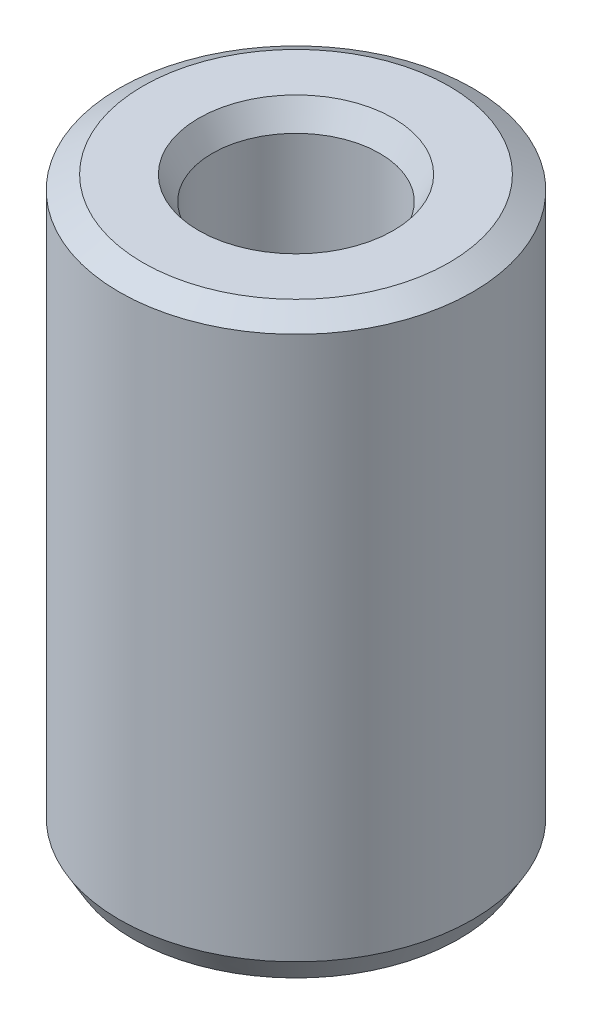
SolidWorks part; units mm, degrees
ref_plane "Front Plane" through (0, 0, 0) normal (0, 0, 1) x (1, 0, 0)
ref_plane "Top Plane" through (0, 0, 0) normal (0, 1, 0) x (1, 0, 0)
ref_plane "Right Plane" through (0, 0, 0) normal (1, 0, 0) x (0, 0, -1)
sketch "Sketch1" plane through (0, 0, 0) normal (0, 1, 0) x (1, 0, 0)
  circle A0 centre (0, 0) radius 35
  dimension "SLEEVE_OD" = 70
extrude "Boss-Extrude1" add sketch "Sketch1" along normal blind 115.0496
sketch "Sketch2" plane through (0, 0, 0) normal (0, 1, 0) x (1, 0, 0)
  circle A0 centre (0, 0) radius 16.5861
  dimension "BORE_D" = 33.1722
extrude "Cut-Extrude1" cut sketch "Sketch2" along normal through all
chamfer "Chamfer1" distance 2.7017 angle 60 4 edges at (0, 115.0496, 16.5861) (0, 0, 16.5861) (0, 0, 35) (0, 115.0496, 35) first distance on face at (0, 115.0496, 16.5861) first distance on face at (0, 0, 16.5861) first distance on face at (0, 115.0496, 35)
